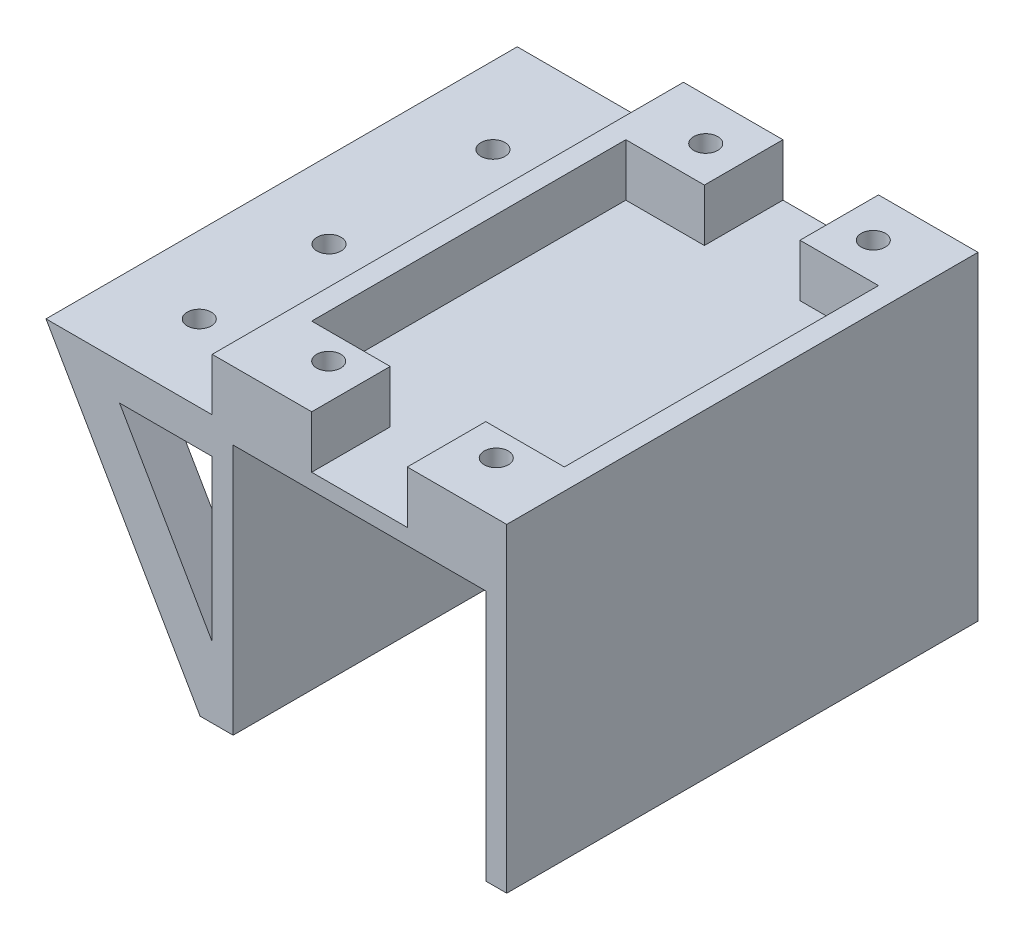
SolidWorks part; units mm, degrees
ref_plane "Front" through (0, 0, 0) normal (0, 0, 1) x (1, 0, 0)
ref_plane "Top" through (0, 0, 0) normal (0, 1, 0) x (1, 0, 0)
ref_plane "Right" through (0, 0, 0) normal (1, 0, 0) x (0, 0, -1)
sketch "Sketch1" plane through (0, 0, 0) normal (0, 0, 1) x (1, 0, 0)
  line L0 (0, 0) -> (0, 70)
  line L1 (0, 70) -> (56.254, 70)
  line L2 (56.254, 70) -> (56.254, 0)
  line L3 (56.254, 0) -> (52.254, 0)
  line L4 (52.254, 0) -> (52.254, 65)
  line L5 (52.254, 65) -> (4, 65)
  line L6 (4, 65) -> (4, 0)
  line L7 (4, 0) -> (0, 0)
  line L9 (4, 55) -> (52.254, 55)
  line L10 (4, 55) -> (4, 52)
  line L11 (4, 52) -> (52.254, 52)
  line L12 (52.254, 55) -> (52.254, 52)
  dimension "D1" = 48.254
  dimension "D2" = 4
  dimension "D3" = 4
  dimension "D4" = 5
  dimension "D5" = 70
  dimension "D6" = 3
  dimension "D7" = 10
extrude "Boss-Extrude1" add sketch "Sketch1" along normal blind 70 contours L7 L6 L5 L4 L3 L2 L1 L0 | L9 L12 L11 L10 region at (0.898, 35, 0)
sketch "Sketch3" plane through (0, 0, 70) normal (0, 0, 1) x (1, 0, 0)
  line L0 (0, 70) -> (-40.3946, 70)
  line L1 (-40.3946, 70) -> (0, 0.0344)
  line L2 (0, 0) -> (0, 70) construction
  line L3 (0, 0.0344) -> (0, 70)
  line L4 (0, 70) -> (0, 62.5)
  line L5 (0, 62.5) -> (-26, 62.5)
  line L6 (-26, 62.5) -> (0, 17.4667)
  line L7 (0, 17.4667) -> (0, 0.0344)
  line M11 (0, 70) -> (0, 0)
  dimension "D1" = 60
  dimension "D2" = 180
  dimension "D3" = 7.5
  dimension "D4" = 26
extrude "Boss-Extrude3" add sketch "Sketch3" against normal blind 8 contours L6 L5 L0 L1 M11 region at (-16.8587, 46.1047, 70)
sketch "Sketch4" plane through (0, 0, 0) normal (0, 0, -1) x (-1, 0, 0)
  line L0 (0, 70) -> (40.3946, 70)
  line L1 (40.3946, 70) -> (0, 0)
  line L2 (0, 0) -> (0, 17.4667)
  line L3 (0, 17.4667) -> (26, 62.5)
  line L4 (26, 62.5) -> (0, 62.5)
  line L5 (0, 62.5) -> (0, 70)
extrude "Boss-Extrude4" add sketch "Sketch4" against normal blind 8
ref_plane "Plane1" through (0, 0, 39) normal (0, 0, -1) x (-1, 0, 0)
sketch "Sketch5" plane through (0, 0, 39) normal (0, 0, -1) x (-1, 0, 0)
  line L0 (0, 62.5) -> (0, 70)
  line L1 (0, 70) -> (40.3946, 70)
  line L2 (40.3946, 70) -> (0, 0)
  line L3 (0, 0) -> (0, 17.4667)
  line L4 (0, 17.4667) -> (26, 62.5)
  line L5 (26, 62.5) -> (0, 62.5)
extrude "Boss-Extrude5" add sketch "Sketch5" along normal blind 8
sketch "Sketch6" plane through (0, 0, 0) normal (0, 0, -1) x (-1, 0, 0)
  line L5 (0, 62.5) -> (36.0666, 62.5)
  line L6 (0, 0) -> (40.3946, 70) construction
  line L7 (36.0666, 62.5) -> (40.3946, 70)
  line L8 (40.3946, 70) -> (0, 70)
  line L9 (40.3946, 70) -> (-56.254, 70) construction
  line L10 (0, 70) -> (0, 62.5)
  line L11 (-4, 0) -> (0, 0)
  line L12 (0, 0) -> (7.5019, 13)
  line L13 (7.5019, 13) -> (-4, 13)
  line L14 (-4, 52) -> (-4, 0) construction
  line L15 (-4, 13) -> (-4, 0)
  dimension "D1" = 13
extrude "Boss-Extrude6" add sketch "Sketch6" against normal blind 70
sketch "Sketch7" plane through (0, 0, 70) normal (0, 0, 1) x (1, 0, 0)
  line L0 (0, 17.4667) -> (0, 62.5) construction
  line L1 (-40.3946, 70) -> (0, 70)
  line L2 (-40.3946, 70) -> (-40.3946, 53)
  line L3 (-40.3946, 53) -> (0, 53)
  line L4 (0, 70) -> (0, 53)
  dimension "D1" = 17
extrude "Cut-Extrude3" cut sketch "Sketch7" against normal blind 70
sketch "Sketch8" plane through (0, 0, 0) normal (0, 0, -1) x (-1, 0, 0)
  line L1 (-4, 55) -> (-4, 52)
  line L2 (-4, 52) -> (-52.254, 52) construction
  line L3 (-4, 52) -> (30.0074, 52)
  line L4 (0, 0) -> (30.5845, 53) construction
  line L6 (30.0074, 52) -> (31.7386, 55)
  line L7 (31.7386, 55) -> (-4, 55)
  dimension "D1" = 180
extrude "Boss-Extrude7" add sketch "Sketch8" against normal blind 70
sketch "Sketch11" plane through (0, 0, 70) normal (0, 0, 1) x (1, 0, 0)
  line L0 (-31.7386, 55) -> (0, 0)
  line L3 (-31.7386, 55) -> (0, 55) construction
  line L4 (-27.289, 55) -> (-31.7386, 55)
  line L5 (-27.289, 55) -> (-3.0537, 13)
  line L6 (-3.0537, 13) -> (0, 0)
extrude "Boss-Extrude10" add sketch "Sketch11" against normal blind 8
sketch "Sketch12" plane through (0, 0, 70) normal (0, 0, 1) x (1, 0, 0)
  line L0 (-31.7386, 55) -> (-27.7598, 48.1051)
  line L1 (0, 0) -> (-31.7386, 55) construction
  line L2 (-27.7598, 48.1051) -> (0, 48.1051)
  line L3 (0, 17.4667) -> (0, 52) construction
  line L4 (0, 48.1051) -> (0, 55)
  line L5 (0, 55) -> (-31.7386, 55)
extrude "Boss-Extrude11" add sketch "Sketch12" against normal blind 70
sketch "Sketch13" plane through (0, 0, 0) normal (0, -1, 0) x (1, 0, 0)
  line L1 (67.4394, -10.6205) -> (-15.562, -10.6205)
  line L2 (67.4394, -10.6205) -> (67.4394, 77.2481)
  line L3 (67.4394, 77.2481) -> (-15.562, 77.2481)
  line L4 (-15.562, -10.6205) -> (-15.562, 77.2481)
extrude "Cut-Extrude4" cut sketch "Sketch13" against normal blind 4
sketch "Sketch14" plane through (0, 0, 70) normal (0, 0, 1) x (1, 0, 0)
  line L0 (-2.3083, 4) -> (-31.7386, 55)
  line L1 (-31.7386, 55) -> (0, 55)
  line L2 (0, 55) -> (0, 70)
  line L3 (0, 70) -> (56.254, 70)
  line L4 (56.254, 70) -> (56.254, 4)
  line L5 (56.254, 4) -> (52.254, 4)
  line L6 (52.254, 4) -> (52.254, 52)
  line L7 (52.254, 52) -> (4, 52)
  line L8 (4, 52) -> (4, 4)
  line L9 (4, 4) -> (-2.3083, 4)
  line L14 (-17.6891, 48.1051) -> (0, 48.1051)
  line L15 (52.254, 55) -> (4, 55)
  line L16 (52.254, 55) -> (52.254, 65)
  line L17 (52.254, 65) -> (4, 65)
  line L18 (4, 55) -> (4, 65)
  line L19 (-17.6891, 48.1051) -> (0, 48.1051) construction
  line L20 (0, 48.1051) -> (0, 17.4667)
  line L21 (0, 17.4667) -> (-17.6891, 48.1051)
extrude "Boss-Extrude12" add sketch "Sketch14" along normal blind 20
sketch "Sketch15" plane through (0, 0, 90) normal (0, 0, 1) x (1, 0, 0)
  line L0 (56.254, 4) -> (56.254, 70) construction
  line L1 (56.254, 65) -> (37.264, 65)
  line L2 (56.254, 65) -> (56.254, 55)
  line L3 (56.254, 55) -> (37.264, 55)
  line L4 (37.264, 65) -> (37.264, 55)
  line L5 (4, 55) -> (52.254, 55) construction
  dimension "D1" = 18.99
sketch "Sketch16" plane through (0, 0, 90) normal (0, 0, 1) x (1, 0, 0)
  line L1 (0, 70) -> (56.254, 70)
  line L2 (0, 70) -> (0, 65)
  line L3 (0, 65) -> (56.254, 65)
  line L4 (56.254, 70) -> (56.254, 65)
extrude "Cut-Extrude5" cut sketch "Sketch16" against normal blind 100
sketch "Sketch17" plane through (0, 65, 0) normal (0, 1, 0) x (1, 0, 0)
  line L1 (52.254, 0) -> (37.254, 0)
  line L2 (52.254, 0) -> (52.254, -15)
  line L3 (52.254, -15) -> (37.254, -15)
  line L4 (37.254, 0) -> (37.254, -15)
  line L5 (52.254, -90) -> (37.254, -90)
  line L6 (52.254, -90) -> (52.254, -75)
  line L7 (52.254, -75) -> (37.254, -75)
  line L8 (37.254, -90) -> (37.254, -75)
  dimension "D1" = 15
  dimension "D2" = 15
  dimension "D3" = 15
  dimension "D4" = 15
extrude "Boss-Extrude14" add sketch "Sketch17" against normal blind 13
sketch "Sketch21" plane through (0, 52, 0) normal (0, -1, 0) x (-1, 0, 0)
  circle A0 centre (-44.254, -80) radius 2.3
  circle A1 centre (-44.254, -8) radius 2.3
sketch "Sketch22" plane through (0, 52, 0) normal (0, -1, 0) x (1, 0, 0)
  line L1 (48.0965, 6.0036) -> (47.9041, 10.3295)
  line L2 (47.9041, 10.3295) -> (44.0617, 12.3259)
  line L3 (44.0617, 12.3259) -> (40.4115, 9.9964)
  line L4 (40.4115, 9.9964) -> (40.6039, 5.6705)
  line L5 (40.6039, 5.6705) -> (44.4463, 3.6741)
  line L6 (44.4463, 3.6741) -> (48.0965, 6.0036)
  line L7 (45.2007, 75.7746) -> (48.3866, 78.7072)
  line L8 (48.3866, 78.7072) -> (47.4399, 82.9325)
  line L9 (47.4399, 82.9325) -> (43.3073, 84.2254)
  line L10 (43.3073, 84.2254) -> (40.1214, 81.2928)
  line L11 (40.1214, 81.2928) -> (41.0681, 77.0675)
  line L12 (41.0681, 77.0675) -> (45.2007, 75.7746)
  circle A0 centre (44.254, 8) radius 3.75 construction
  circle A1 centre (44.254, 80) radius 3.75 construction
  point P10 (42.2366, 11.1611)
  dimension "D1" = 7.5
  dimension "D2" = 7.5
extrude "Cut-Extrude8" cut sketch "Sketch22" against normal blind 5
extrude "Cut-Extrude9" cut sketch "Sketch21" against normal blind 15
sketch "Sketch23" plane through (0, 0, 0) normal (-0.8661, -0.4998, 0) x (0, 0, 1)
  line L0 (90, 63.5007) -> (90, 4.6182) construction
  line L1 (70, 55.5401) -> (82, 55.5401)
  line L2 (70, 55.5401) -> (70, 15.0093)
  line L3 (70, 15.0093) -> (82, 15.0093)
  line L4 (82, 55.5401) -> (82, 15.0093)
  line L5 (62, 55.5401) -> (62, 15.0093) construction
  dimension "D1" = 8
  dimension "D2" = 8
extrude "Cut-Extrude10" cut sketch "Sketch23" against normal blind 9
sketch "Sketch25" plane through (0, 48.1051, 0) normal (0, -1, 0) x (-1, 0, 0)
  circle A0 centre (17.0755, -19.3006) radius 2.3
  circle A1 centre (17.0755, -50.6137) radius 2.3
extrude "Cut-Extrude11" cut sketch "Sketch25" against normal blind 20
sketch "Sketch26" plane through (0, 48.1051, 0) normal (0, -1, 0) x (1, 0, 0)
  circle A0 centre (-17.0755, 75.3913) radius 2.3
extrude "Cut-Extrude12" cut sketch "Sketch26" against normal blind 20
sketch "Sketch27" plane through (0, 0, 90) normal (0, 0, 1) x (1, 0, 0)
  line L0 (-23.3104, 48.1051) -> (-27.7598, 48.1051)
  line L1 (-31.7386, 55) -> (-2.3083, 4) construction
  line L2 (-27.7598, 48.1051) -> (-31.7386, 55)
  line L3 (-31.7386, 55) -> (-23.3104, 55)
  line L4 (0, 55) -> (-31.7386, 55) construction
  line L5 (-23.3104, 55) -> (-23.3104, 48.1051)
extrude "Boss-Extrude16" add sketch "Sketch27" against normal blind 20
sketch "Sketch28" plane through (0, 55, 0) normal (0, 1, 0) x (1, 0, 0)
  line L0 (4, -90) -> (37.254, -90) construction
  line L1 (4, 0) -> (19, 0)
  line L2 (4, 0) -> (4, -15)
  line L3 (4, -15) -> (19, -15)
  line L4 (19, 0) -> (19, -15)
  line L5 (4, -90) -> (19, -90)
  line L6 (4, -90) -> (4, -75)
  line L7 (4, -75) -> (19, -75)
  line L8 (19, -90) -> (19, -75)
  line L9 (4, 0) -> (4, -90) construction
  dimension "D1" = 15
  dimension "D2" = 15
  dimension "D3" = 15
  dimension "D4" = 15
extrude "Boss-Extrude17" add sketch "Sketch28" along normal blind 10
sketch "Sketch29" plane through (0, 52, 0) normal (0, -1, 0) x (-1, 0, 0)
  circle A0 centre (-12.254, -8) radius 2.3
  circle A1 centre (-12.254, -80) radius 2.3
extrude "Cut-Extrude13" cut sketch "Sketch29" against normal blind 20
sketch "Sketch30" plane through (0, 48.1051, 0) normal (0, -1, 0) x (1, 0, 0)
  line L1 (-27.7598, 70) -> (-17.3688, 70)
  line L2 (-27.7598, 70) -> (-27.7598, 82)
  line L3 (-27.7598, 82) -> (-17.3688, 82)
  line L4 (-17.3688, 70) -> (-17.3688, 82)
extrude "Boss-Extrude18" add sketch "Sketch30" against normal blind 5
sketch "Sketch31" plane through (0, 48.1051, 0) normal (0, -1, 0) x (1, 0, 0)
  circle A0 centre (-17.0755, 75.3913) radius 2.3
extrude "Cut-Extrude14" cut sketch "Sketch31" against normal blind 45
